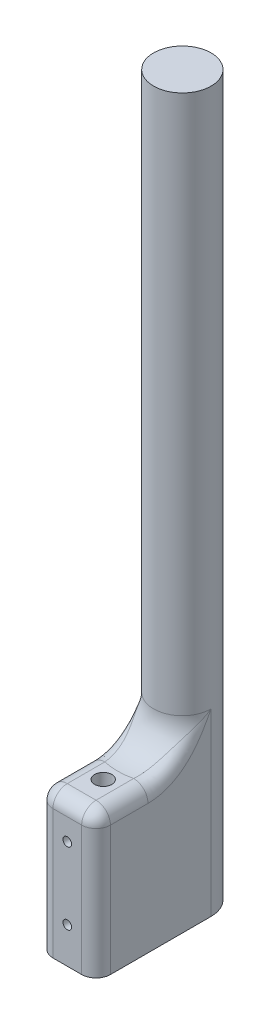
SolidWorks part; units mm, degrees
ref_plane "Front Plane" through (0, 0, 0) normal (0, 0, 1) x (1, 0, 0)
ref_plane "Top Plane" through (0, 0, 0) normal (0, 1, 0) x (1, 0, 0)
ref_plane "Right Plane" through (0, 0, 0) normal (1, 0, 0) x (0, 0, -1)
sketch "Sketch1" plane through (0, 0, 0) normal (0, 1, 0) x (1, 0, 0)
  line L0 (0, 0) -> (4, -10) construction
  line L2 (-4, 6) -> (-4, -10)
  line L3 (-4, -10) -> (4, -10)
  line L4 (4, 6) -> (4, -10)
  line L5 (-3.3027, 8.2566) -> (-0.8353, 2.0882) construction
  line L6 (-4, -10) -> (3.3027, 8.2566) construction
  arc A0 (4, 6) -> (-4, 6) centre (0, 6) ccw
  circle A1 centre (0, -5) radius 1.2
  point P0 (0, 0)
  dimension "D1" = 5
extrude "Boss-Extrude1" add sketch "Sketch1" against normal blind 20
sketch "Sketch2" plane through (0, 0, 0) normal (0, 1, 0) x (1, 0, 0)
  circle A0 centre (0, 6) radius 4
extrude "Boss-Extrude2" add sketch "Sketch2" along normal blind 80
fillet "Fillet1" radius 5 1 edges
fillet "Fillet2" radius 2 7 edges at (4, 0.3935, -0.1877) (-4, 0.3935, -0.1877) (-4, -10, 10) (4, -10, 10) (0, 0, 10)
sketch "Sketch3" plane through (0, 0, 10) normal (0, 0, 1) x (1, 0, 0)
  line L0 (2, 0) -> (-2, 0) construction
  line L1 (-2, -20) -> (2, -20) construction
  circle A0 centre (0, -5) radius 0.6
  circle A1 centre (0, -15) radius 0.6
  dimension "D1" = 5
  dimension "D2" = 5
extrude "Cut-Extrude1" cut sketch "Sketch3" against normal through all
